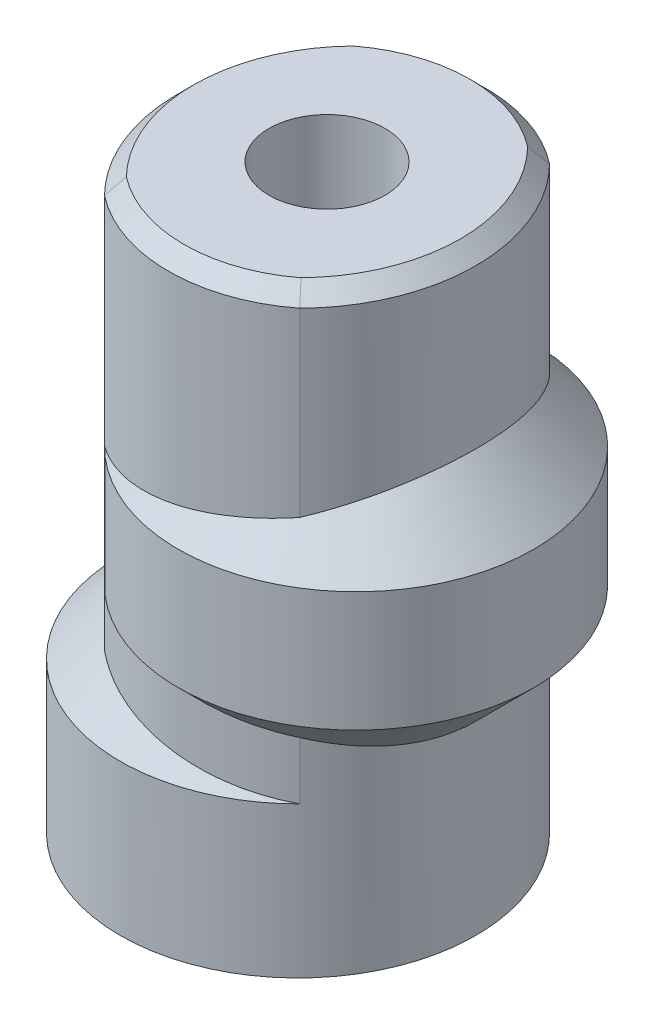
SolidWorks part; units mm, degrees
material "ABS"
ref_plane "Front Plane" through (0, 0, 0) normal (0, 0, 1) x (1, 0, 0)
ref_plane "Top Plane" through (0, 0, 0) normal (0, 1, 0) x (1, 0, 0)
ref_plane "Right Plane" through (0, 0, 0) normal (1, 0, 0) x (0, 0, -1)
sketch "Sketch1" plane through (0, 0, 0) normal (0, 1, 0) x (1, 0, 0)
  line L0 (0.75, 0) -> (0, 0) construction
  line L1 (0, 0) -> (-0.75, 0) construction
  arc A0 (-2.525, -3.2302) -> (2.525, -3.2302) centre (0, 0) ccw
  arc A1 (-2.525, 3.2302) -> (-2.525, -3.2302) centre (0.75, 0) ccw
  arc A2 (2.525, 3.2302) -> (2.525, -3.2302) centre (-0.75, 0) cw
  arc A3 (2.525, 3.2302) -> (-2.525, 3.2302) centre (0, 0) ccw
  dimension "D1" = 8.2
  dimension "D3" = 4.6
  dimension "D5" = 4.6
  dimension "D2" = 0.75
  dimension "D4" = 0.75
extrude "Boss-Extrude1" add sketch "Sketch1" along normal blind 15.4
sketch "Sketch2" plane through (0, 0, 0) normal (0, 0, 1) x (1, 0, 0)
  line L0 (3.85, 0) -> (3.85, 3.9)
  line L1 (2.35, 5.4) -> (-0.75, 5.4)
  line L2 (-0.75, 5.4) -> (-0.75, 0)
  line L3 (-0.75, 0) -> (3.85, 0)
  line L4 (-2.525, 0) -> (2.525, 0) construction
  line L5 (3.85, 3.9) -> (2.35, 5.4)
  line L7 (2.35, 2.7) -> (-3.85, 2.7) construction
  line L8 (-3.85, 15.4) -> (-3.85, 0) construction
  point P0 (3.85, 0)
  point P1 (3.85, 5.4)
  point P16 (-0.75, 2.7)
  dimension "D1" = 0.75
  dimension "D2" = 5.4
  dimension "D3" = 4.6
revolve "Revolve1" add sketch "Sketch2" angle 360 about L2
sketch "Sketch3" plane through (0, 0, 0) normal (0, 0, 1) x (1, 0, 0)
  line L0 (-5.35, 0) -> (3.85, 0) construction
  line L1 (0.75, 4.8) -> (-2.35, 4.8)
  line L2 (0.75, 4.8) -> (0.75, 10.9)
  line L3 (0.75, 10.9) -> (-2.35, 10.9)
  line L4 (-3.85, 6.3) -> (-3.85, 9.4)
  line L6 (-2.35, 10.9) -> (-3.85, 9.4)
  line L7 (-2.35, 4.8) -> (-3.85, 6.3)
  point P1 (-3.85, 10.9)
  point P3 (-3.85, 4.8)
  dimension "D1" = 0.75
  dimension "D2" = 6.1
  dimension "D3" = 4.6
  dimension "D4" = 4.8
revolve "Revolve2" add sketch "Sketch3" angle 360 about L2
sketch "Sketch4" plane through (0, 0, 0) normal (0, -1, 0) x (1, 0, 0)
  line L1 (0, 2.5) -> (0, -1.9) construction
  line L3 (-2, -1.9) -> (2, -1.9) construction
  line L4 (-2, -2) -> (2, -2)
  arc A0 (2.2136, -1.1618) -> (-2.2136, -1.1618) centre (0, 0) ccw construction
  arc A2 (-2, -1.9) -> (-2.2136, -1.1618) centre (-2, -1.5) cw construction
  arc A3 (2, -1.9) -> (2.2136, -1.1618) centre (2, -1.5) ccw construction
  arc A4 (2, -2) -> (2.34, -1.1334) centre (2, -1.5) ccw
  arc A5 (2.34, -1.1334) -> (-2.34, -1.1334) centre (0, 0) ccw
  arc A6 (-2, -2) -> (-2.34, -1.1334) centre (-2, -1.5) cw
  point P14 (0, -1.9)
  dimension "D1" = 2.5
  dimension "D3" = 0.4
  dimension "D4" = 0.1
  dimension "D2" = 4.4
extrude "Cut-Extrude1" cut sketch "Sketch4" against normal offset from surface (11.8 mm away) 3.6 up to face at (0, 15.4, 0)
sketch "Sketch5" plane through (0, 15.4, 0) normal (0, 1, 0) x (1, 0, 0)
  circle A0 centre (0, 0) radius 1.5
  dimension "D1" = 3
extrude "Cut-Extrude2" cut sketch "Sketch5" against normal up to next
chamfer "Chamfer1" distance 0.4 angle 45 4 edges at (0, 15.4, -4.1) (-3.85, 15.4, 0) (0, 15.4, 4.1) (3.85, 15.4, 0)
